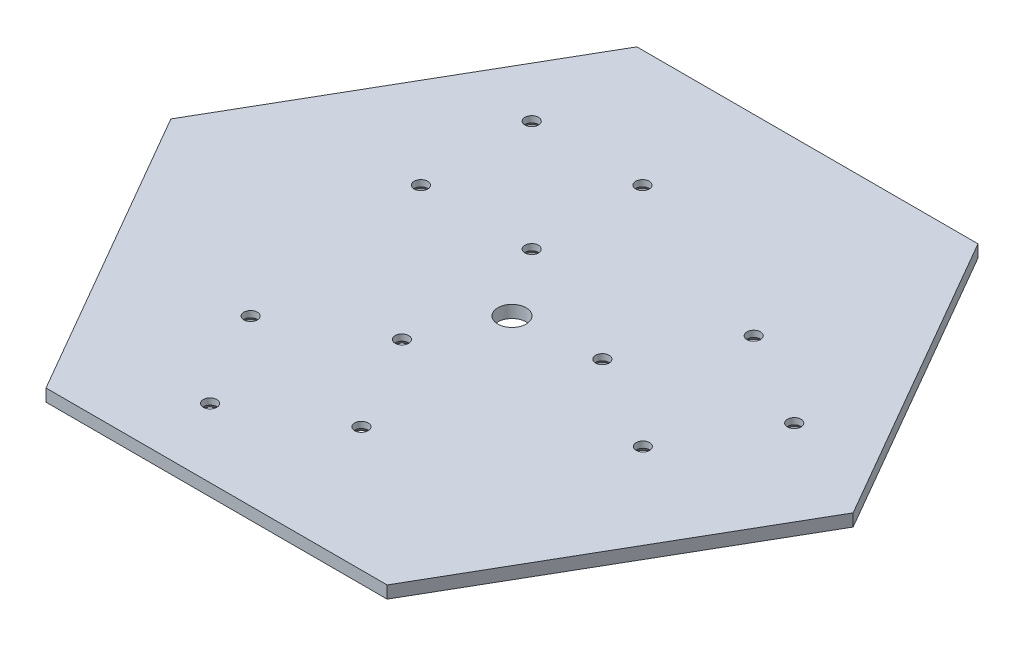
SolidWorks part; units mm, degrees
ref_plane "Front Plane" through (0, 0, 0) normal (0, 0, 1) x (1, 0, 0)
ref_plane "Top Plane" through (0, 0, 0) normal (0, 1, 0) x (1, 0, 0)
ref_plane "Right Plane" through (0, 0, 0) normal (1, 0, 0) x (0, 0, -1)
sketch "Sketch1" plane through (0, 0, 0) normal (0, 1, 0) x (1, 0, 0)
  line L1 (69.282, 120) -> (-69.282, 120)
  line L2 (-69.282, 120) -> (-138.5641, 0)
  line L3 (-138.5641, 0) -> (-69.282, -120)
  line L4 (-69.282, -120) -> (69.282, -120)
  line L5 (69.282, -120) -> (138.5641, 0)
  line L6 (138.5641, 0) -> (69.282, 120)
  circle A0 centre (0, 0) radius 120 construction
  dimension "D1" = 240
extrude "Boss-Extrude1" add sketch "Sketch1" along normal blind 5
sketch "Sketch2" plane through (0, 0, 0) normal (0, 1, 0) x (1, 0, 0)
  line L0 (0, 0) -> (103.923, 60) construction
  line L1 (138.5641, 0) -> (69.282, 120) construction
  line L2 (75.5513, 30.8586) -> (53.0513, -8.1125) construction
  line L3 (66.5368, -29.7548) -> (27.5657, -7.2548) construction
  line L6 (33.5657, 3.1375) -> (72.5368, -19.3625) construction
  line L7 (72.5368, -19.3625) -> (95.0368, 19.6086) construction
  line L8 (95.0368, 19.6086) -> (56.0657, 42.1086) construction
  line L9 (56.0657, 42.1086) -> (33.5657, 3.1375) construction
  line L10 (-14.0657, -30.6375) -> (-53.0368, -53.1375) construction
  line L11 (8.4343, -69.6086) -> (-14.0657, -30.6375) construction
  line L12 (-30.5368, -92.1086) -> (8.4343, -69.6086) construction
  line L13 (-53.0368, -53.1375) -> (-30.5368, -92.1086) construction
  line L14 (-19.5, 27.5) -> (-19.5, 72.5) construction
  line L15 (-64.5, 27.5) -> (-19.5, 27.5) construction
  line L16 (-64.5, 72.5) -> (-64.5, 27.5) construction
  line L17 (-19.5, 72.5) -> (-64.5, 72.5) construction
  line L19 (53.0513, -8.1125) -> (43.3013, -25) construction
  line L21 (103.923, -60) -> (0, 0) construction
  line L22 (69.282, -120) -> (138.5641, 0) construction
  point P9 (47.0513, -18.5048)
  point P18 (33.5657, 3.1375)
  point P19 (56.0657, 42.1086)
  point P20 (95.0368, 19.6086)
  point P21 (72.5368, -19.3625)
  point P31 (0, 0)
  dimension "D1" = 45
  dimension "D2" = 45
  dimension "D4" = 7.5
  dimension "D5" = 12
  dimension "D6" = 50
  dimension "D3" = 3
sketch "Sketch5" plane through (0, 5, 0) normal (0, 1, 0) x (1, 0, 0)
  circle A0 centre (0, 0) radius 5.7532
extrude "Cut-Extrude1" cut sketch "Sketch5" against normal through all
hole_wizard "CSK for M5 Flat Head Machine Screw1" positions "Sketch7" profile "Sketch6" countersink size "M5" standard "ANSI Metric" end condition through all
sketch "Sketch7" plane through (0, 0, 0) normal (0, -1, 0) x (-1, 0, 0)
  point P0 (64.5, 27.5)
  point P3 (19.5, 27.5)
  point P6 (19.5, 72.5)
  point P9 (64.5, 72.5)
  point P12 (-33.5657, 3.1375)
  point P15 (-72.5368, -19.3625)
  point P18 (-95.0368, 19.6086)
  point P21 (-56.0657, 42.1086)
  point P24 (14.0657, -30.6375)
  point P27 (-8.4343, -69.6086)
  point P30 (30.5368, -92.1086)
  point P33 (53.0368, -53.1375)
sketch "Sketch6" plane through (-64.5, 0, -27.5) normal (1, 0, 0) x (0, 0, -1)
  line L0 (0, 0) -> (0, 5)
  line L1 (0, 5) -> (2.75, 5)
  line L2 (2.75, 5) -> (2.75, 2.45)
  line L3 (2.75, 2.45) -> (5.2, 0)
  line L5 (5.2, 0) -> (0, 0)
  line L6 (-2.75, 2.45) -> (-5.2, 0) construction
  line L11 (0, -6.35) -> (0, 107.95) construction
  dimension "Thru Hole Dia." = 5.5
  dimension "Thru Hole Depth" = 5
  dimension "Near C'Sink Dia." = 10.4
  dimension "Near C'Sink Angle" = 90
